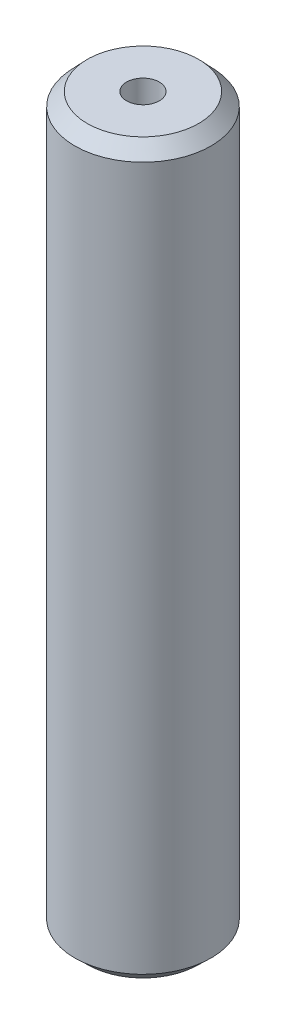
SolidWorks part; units mm, degrees
ref_plane "Front Plane" through (0, 0, 0) normal (0, 0, 1) x (1, 0, 0)
ref_plane "Top Plane" through (0, 0, 0) normal (0, 1, 0) x (1, 0, 0)
ref_plane "Right Plane" through (0, 0, 0) normal (1, 0, 0) x (0, 0, -1)
sketch "Sketch1" plane through (0, 0, 0) normal (0, 1, 0) x (1, 0, 0)
  circle A0 centre (0, 0) radius 5
  dimension "SHAFT_OD" = 10
extrude "Boss-Extrude1" add sketch "Sketch1" along normal blind 53.49
sketch "Sketch2" plane through (0, 0, 0) normal (0, 1, 0) x (1, 0, 0)
  circle A0 centre (0, 0) radius 1.2002
  dimension "BORE_D" = 2.4004
extrude "Cut-Extrude1" cut sketch "Sketch2" along normal through all
chamfer "Chamfer1" distance 0.9655 angle 43.493 2 edges at (0, 53.49, 5) (0, 0, 5) first distance on face at (0, 53.49, 5) first distance on face at (0, 0, 1.2002)
